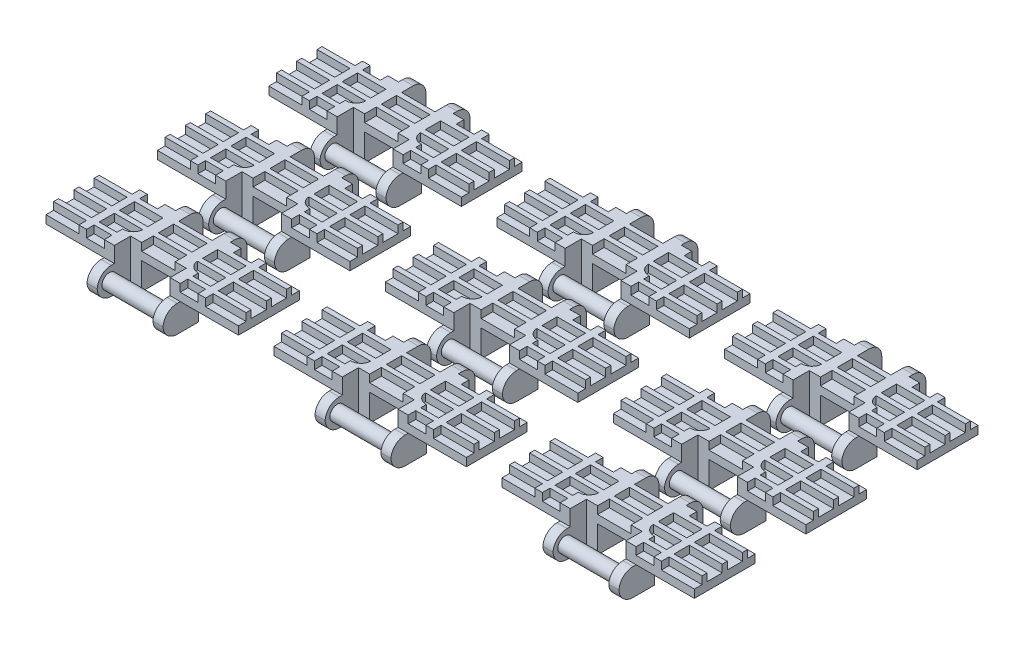
SolidWorks part; units mm, degrees
ref_plane "前视基准面" through (0, 0, 0) normal (0, 0, 1) x (1, 0, 0)
ref_plane "上视基准面" through (0, 0, 0) normal (0, 1, 0) x (1, 0, 0)
ref_plane "右视基准面" through (0, 0, 0) normal (1, 0, 0) x (0, 0, -1)
other "Configuration Table"
sketch "草图1" plane through (0, 0, 0) normal (0, 1, 0) x (1, 0, 0)
  line L1 (-19, -6) -> (19, -6)
  line L2 (-19, -6) -> (-19, 6)
  line L3 (-19, 6) -> (19, 6)
  line L4 (19, -6) -> (19, 6)
  line L5 (-19, -6) -> (19, 6) construction
  line L6 (-19, 6) -> (19, -6) construction
  line L13 (-19, 4.5) -> (19, 4.5)
  line L14 (-19, 4.5) -> (-19, 3.5)
  line L15 (-19, 3.5) -> (19, 3.5)
  line L16 (19, 4.5) -> (19, 3.5)
  line L17 (-19, 0.5) -> (19, 0.5)
  line L18 (-19, 0.5) -> (-19, -0.5)
  line L19 (-19, -0.5) -> (19, -0.5)
  line L20 (19, 0.5) -> (19, -0.5)
  line L21 (-19, -3.5) -> (19, -3.5)
  line L22 (-19, -3.5) -> (-19, -4.5)
  line L23 (-19, -4.5) -> (19, -4.5)
  line L24 (19, -3.5) -> (19, -4.5)
  line L25 (-12.5, 6) -> (-11, 6)
  line L26 (-12.5, 6) -> (-12.5, -6)
  line L27 (-12.5, -6) -> (-11, -6)
  line L28 (-11, 6) -> (-11, -6)
  line L29 (12.5, 6) -> (11, 6)
  line L30 (12.5, 6) -> (12.5, -6)
  line L31 (12.5, -6) -> (11, -6)
  line L32 (11, 6) -> (11, -6)
  point P0 (0, 0)
  point P6 (0, 0)
  dimension "D1" = 38
  dimension "D2" = 12
  dimension "D3" = 11
  dimension "D4" = 11
  dimension "D5" = 1
  dimension "D6" = 1.5
  dimension "D7" = 1.5
  dimension "D8" = 5.5
  dimension "D9" = 1.5
extrude "凸台-拉伸1" add sketch "草图1" along normal blind 1.6 contours L2 L3 L4 L1
extrude "凸台-拉伸2" add sketch "草图1<3>" along normal blind 1.5 from surface contours L13 L16 L15 L14 | L17 L20 L19 L18 | L21 L24 L23 L22 | L26 L27 L28 L25 | L30 L31 L32 L29 starting at face at (0, 1.6, 0)
sketch "草图1<3>" plane through (0, 0, 0) normal (0, 1, 0) x (1, 0, 0) same geometry as "草图1"
sketch "草图2" plane through (0, 0, 0) normal (0, 1, 0) x (1, 0, 0)
  line L0 (0, 0) -> (0, -13.8005) construction
  line L1 (-5.4, 9.3) -> (5.4, 9.3)
  line L2 (-5.4, 9.3) -> (-5.4, -2.8)
  line L3 (-5.4, -2.8) -> (5.4, -2.8)
  line L4 (5.4, 9.3) -> (5.4, -2.8)
  line L5 (-7.5, -2.8) -> (7.5, -2.8)
  line L6 (11, 4.5) -> (-11, 4.5) construction
  line L7 (-7.5, 6) -> (-5.4, 6)
  line L8 (-3.3, 9.3) -> (3.3, 9.3)
  line L9 (-3.3, 9.3) -> (-3.3, -2.8)
  line L10 (-3.3, -2.8) -> (3.3, -2.8)
  line L11 (3.3, 9.3) -> (3.3, -2.8)
  line L16 (-11, -6) -> (11, -6) construction
  line L17 (-11, 6) -> (11, 6) construction
  line L18 (-5.5, -2.4) -> (-5.5, -9.4)
  line L19 (-7.5, -2.4) -> (7.5, -2.4)
  line L20 (-7.5, -2.4) -> (-7.5, -9.4)
  line L21 (-7.5, -9.4) -> (7.5, -9.4)
  line L22 (7.5, -2.4) -> (7.5, -9.4)
  line L23 (5.5, -2.4) -> (5.5, -9.4)
  line L24 (-7.5, 6) -> (-7.5, 4.5)
  line L25 (-7.5, 4.5) -> (-5.4, 4.5)
  line L26 (-5.4, 6) -> (-5.4, 4.5)
  line L27 (7.5, 6) -> (5.4, 6)
  line L28 (7.5, 6) -> (7.5, 4.5)
  line L29 (7.5, 4.5) -> (5.4, 4.5)
  line L30 (5.4, 6) -> (5.4, 4.5)
  point P5 (0, -2.8)
  point P15 (0, 9.3)
  point P20 (0, -9.4)
  dimension "D1" = 10.8
  dimension "D2" = 3.2
  dimension "D3" = 6.6
  dimension "D4" = 3.3
  dimension "D5" = 15
  dimension "D6" = 2
  dimension "D7" = 2
  dimension "D8" = 3.4
  dimension "D9" = 7
extrude "凸台-拉伸3" add sketch "草图2" against normal blind 8.4 from surface contours L1 L11 L3 L4 | L9 L1 L2 L3 | L20 L21 L18 L19 | L19 L23 L21 L22 | L19 L18 L5 L2 | L19 L20 L5 L18 | L19 L2 L3 L9 | L19 L11 L3 L4 | L23 L19 L4 L5 | L19 L23 L5 L22 region at (-4.35, 0, -3.45) region at (4.35, 0, -3.45) region at (-4.35, 0, 2.6) region at (4.35, 0, 2.6) region at (-5.45, 0, 2.6) region at (5.45, 0, 2.6) region at (-6.5, 0, 2.6) region at (6.5, 0, 2.6) region at (-6.5, 0, 6.1) region at (6.5, 0, 6.1) starting at face at (0, 3.1, 0)
extrude "凸台-拉伸5" add sketch "草图2<4>" along normal up to surface (3.1 mm away) contours L27 L30 L29 L28 | L7 L26 L25 L24 up to face at (0, 3.1, -2)
sketch "草图2<4>" plane through (0, 0, 0) normal (0, 1, 0) x (1, 0, 0) same geometry as "草图2"
extrude "切除-拉伸1" cut sketch "草图2<3>" along normal through all contours L0 L5 L3 L18 L21 | L10 L0 L21 L23 L5 L3 region at (2.75, 0, 6.1) region at (-2.75, 0, 6.1)
sketch "草图2<3>" plane through (0, 0, 0) normal (0, 1, 0) x (1, 0, 0) same geometry as "草图2"
fillet "圆角1" radius 3 2 edges at (5.4, -2.65, 2.4) (-5.4, -2.65, 2.4)
sketch "草图3" plane through (-5.5, 0, 0) normal (1, 0, 0) x (0, 0, -1)
  line L2 (-7, -2.5) -> (5.58, -2.5)
  line L3 (2.8, -4.1) -> (9.3, -4.1)
  line L4 (2.8, -4.1) -> (2.8, -5.3)
  line L5 (2.8, -5.3) -> (9.3, -5.3)
  line L6 (9.3, -4.1) -> (9.3, -5.3)
  line L7 (-9.4, -5.3) -> (-9.4, 3.1) construction
  line L8 (-6, 3.1) -> (-9.4, 3.1)
  line L9 (-6, 3.1) -> (-6, 0)
  line L10 (-6, 0) -> (-9.4, 0)
  line L11 (-9.4, 3.1) -> (-9.4, 0)
  circle A0 centre (-7, -2.5) radius 1.45
  circle A1 centre (5.58, -2.5) radius 1.7
  dimension "D1" = 2.9
  dimension "D3" = 3.4
  dimension "D7" = 7
  dimension "D2" = 2.5
  dimension "D4" = 1.2
  dimension "D5" = 6.5
  dimension "D6" = 12.58
extrude "凸台-拉伸4" add sketch "草图3" along normal up to next contours A0
extrude "切除-拉伸2" cut sketch "草图3<3>" along normal through all both and the other way through all contours L3 L6 L5 L4 | A1 | L11 L10 L9 L8
sketch "草图3<3>" plane through (-5.5, 0, 0) normal (1, 0, 0) x (0, 0, -1) same geometry as "草图3"
fillet "圆角2" radius 2.8 4 edges at (6.5, -5.3, 9.4) (-6.5, -5.3, 9.4) (-6.5, 0, 9.4) (6.5, 0, 9.4)
fillet "圆角3" radius 2.5 2 edges at (-4.35, 3.1, -9.3) (4.35, 3.1, -9.3)
fillet "圆角4" radius 1 2 edges at (-4.35, -4.1, -9.3) (4.35, -4.1, -9.3)
fillet "圆角5" radius 0.3 4 edges at (-4.35, -4.1, -6.1545) (4.35, -4.1, -6.1545) (4.35, -4.1, -5.0055) (-4.35, -4.1, -5.0055)
fillet "圆角6" radius 2 2 edges at (5.4, 2.35, 2.4) (-5.4, 2.35, 2.4)
ref_plane "基准面1" through (0, 0, 12) normal (0, 0, 1) x (1, 0, 0)
ref_plane "基准面2" through (22, 0, 0) normal (1, 0, 0) x (0, 0, -1)
pattern_linear "阵列(线性)1" count 3 spacing 22 along (0, 0, 1) of bodies 121
pattern_linear "阵列(线性)2" count 3 spacing 45 along (1, 0, 0) of bodies 121 123 124
